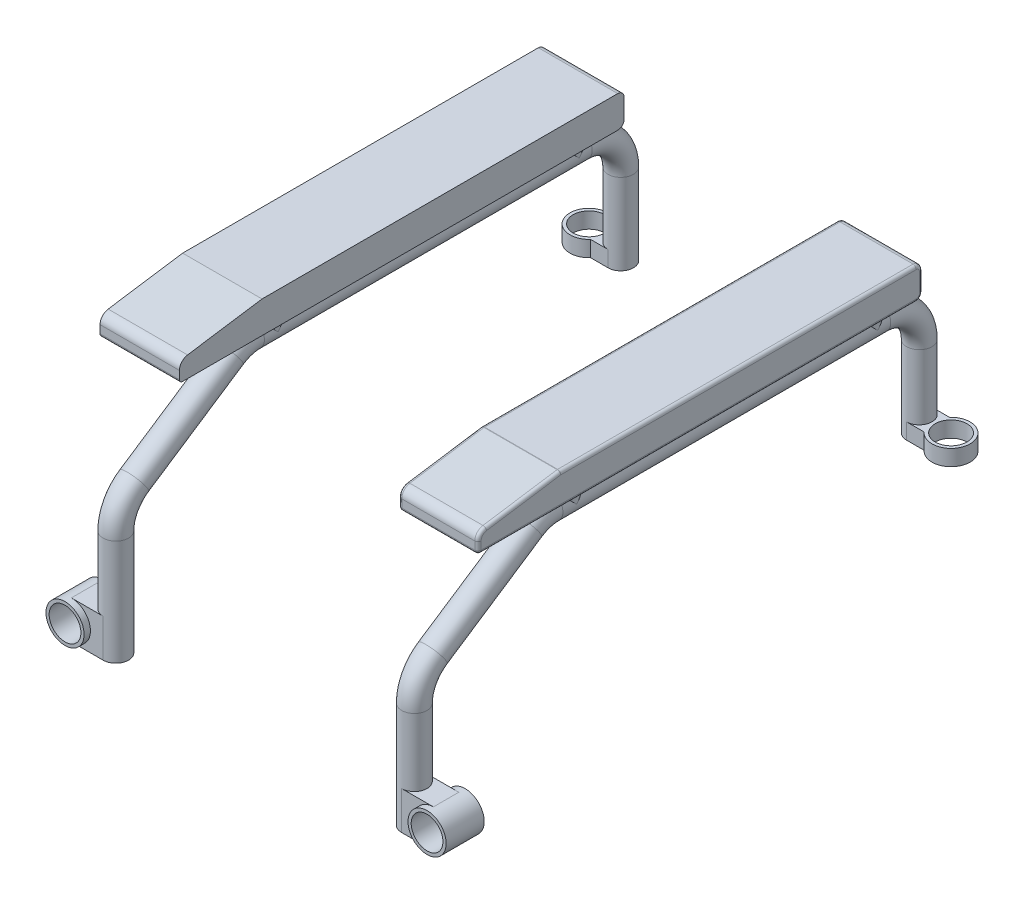
SolidWorks part; units mm, degrees
ref_plane "Front Plane" through (0, 0, 0) normal (0, 0, 1) x (1, 0, 0)
ref_plane "Top Plane" through (0, 0, 0) normal (0, 1, 0) x (1, 0, 0)
ref_plane "Right Plane" through (0, 0, 0) normal (1, 0, 0) x (0, 0, -1)
sketch "Sketch1" plane through (0, 0, 0) normal (1, 0, 0) x (0, 0, -1)
  line L0 (0, 0) -> (342.9, 0) construction
  line L1 (342.9, 0) -> (342.9, 54.61) construction
  line L2 (0, 0) -> (0, 69.3262)
  line L3 (108.6557, 152.4) -> (370.84, 152.4)
  line L4 (403.86, 119.38) -> (403.86, 54.61)
  line L5 (98.7191, 183.1531) -> (98.7191, 100.5217) construction
  line L6 (-22.3454, 87.0701) -> (49.3966, 87.0701) construction
  line L7 (14.7972, 96.8625) -> (90.4328, 146.9163)
  arc A0 (403.86, 119.38) -> (370.84, 152.4) centre (370.84, 119.38) ccw
  arc A1 (108.6557, 152.4) -> (90.4328, 146.9163) centre (108.6557, 119.38) ccw
  arc A2 (0, 69.3262) -> (14.7972, 96.8625) centre (33.02, 69.3262) cw
  point P16 (98.7191, 152.4)
  point P19 (0, 87.0701)
  dimension "D1" = 33.02
  dimension "D2" = 33.02
sketch "Sketch2" plane through (0, 0, 0) normal (0, 1, 0) x (1, 0, 0)
  circle A0 centre (0, 0) radius 10.16
sweep "Sweep1" add profiles "Sketch2" path "Sketch1"
sketch "Sketch3" plane through (0, 0, 0) normal (0, -1, 0) x (1, 0, 0)
  line L0 (0, 0) -> (-25.4, 0)
  line L1 (0, -403.86) -> (-25.4, -403.86)
sketch "Sketch4" plane through (0, 0, 0) normal (0, 0, 1) x (1, 0, 0)
  line L0 (0, 0) -> (-25.4, 0) construction
  circle A0 centre (-25.4, 0) radius 15.24
extrude "Boss-Extrude1" add sketch "Sketch4" along normal blind 15.24 and the other way blind 15.24 separate body
sketch "Sketch5" plane through (0, 0, 0) normal (0, -1, 0) x (1, 0, 0)
  circle A1 centre (0, 0) radius 10.16
  circle A2 centre (0, 0) radius 10.16
  dimension "D1" = 0
extrude "Boss-Extrude2" add sketch "Sketch5" along normal blind 15.24
sketch "Sketch6" plane through (0, 0, 0) normal (1, 0, 0) x (0, 0, -1)
  line L0 (-10.16, -15.24) -> (-10.16, 15.24)
  line L1 (15.24, 15.24) -> (-15.24, 15.24) construction
  line L2 (-10.16, 69.3262) -> (-10.16, -15.24) construction
  line L3 (-10.16, 15.24) -> (10.16, 15.24)
  line L4 (10.16, 15.24) -> (10.16, -15.24)
  line L5 (-10.16, -15.24) -> (10.16, -15.24) construction
  line L6 (10.16, -15.24) -> (-10.16, -15.24)
extrude "Boss-Extrude3" add sketch "Sketch6" against normal blind 25.4
sketch "Sketch7" plane through (0, 0, 15.24) normal (0, 0, 1) x (1, 0, 0)
  circle A0 centre (-25.4, 0) radius 12.7
extrude "Cut-Extrude1" cut sketch "Sketch7" against normal through all
ref_plane "Plane1" through (0, 54.61, 0) normal (0, 1, 0) x (1, 0, 0)
sketch "Sketch8" plane through (0, 54.61, 0) normal (0, 1, 0) x (1, 0, 0)
  circle A0 centre (-25.4, 403.86) radius 15.24
extrude "Boss-Extrude4" add sketch "Sketch8" along normal blind 12.7 separate body
sketch "Sketch10" plane through (0, 0, 0) normal (1, 0, 0) x (0, 0, -1)
  line L0 (393.7, 54.61) -> (414.02, 54.61)
  line L1 (414.02, 54.61) -> (414.02, 67.31)
  line L2 (414.02, 54.61) -> (414.02, 119.38) construction
  line L3 (414.02, 67.31) -> (393.7, 67.31)
  line L4 (393.7, 119.38) -> (393.7, 54.61) construction
  line L5 (393.7, 67.31) -> (393.7, 54.61)
extrude "Boss-Extrude5" add sketch "Sketch10" against normal blind 25.4
sketch "Sketch11" plane through (0, 67.31, 0) normal (0, 1, 0) x (1, 0, 0)
  circle A0 centre (-25.4, 403.86) radius 12.7
extrude "Cut-Extrude2" cut sketch "Sketch11" against normal blind 25.4
ref_plane "Plane2" through (0, 152.4, 0) normal (0, 1, 0) x (1, 0, 0)
sketch "Sketch12" plane through (0, 152.4, 0) normal (0, 1, 0) x (1, 0, 0)
  line L0 (0, 370.84) -> (0, 108.6557) construction
  line L1 (10.16, 370.84) -> (-10.16, 370.84) construction
  line L2 (10.16, 108.6557) -> (-10.16, 108.6557) construction
  circle A0 centre (0, 360.4101) radius 10.16
  circle A1 centre (0, 119.554) radius 10.16
extrude "Boss-Extrude6" add sketch "Sketch12" along normal blind 25.4
sketch "Sketch13" plane through (0, 0, 0) normal (1, 0, 0) x (0, 0, -1)
  line L0 (369.6857, 177.8) -> (21.68, 177.8)
  line L1 (374.7657, 182.88) -> (374.7657, 198.12)
  line L2 (369.6857, 203.2) -> (85.1707, 203.2)
  line L3 (19.14, 180.34) -> (19.14, 186.6826)
  line L4 (25.6234, 194.2174) -> (85.1707, 203.2)
  arc A0 (19.14, 186.6826) -> (25.6234, 194.2174) centre (26.76, 186.6826) cw
  arc A4 (19.14, 180.34) -> (21.68, 177.8) centre (21.68, 180.34) ccw
  arc A5 (374.7657, 182.88) -> (369.6857, 177.8) centre (369.6857, 182.88) cw
  arc A6 (374.7657, 198.12) -> (369.6857, 203.2) centre (369.6857, 198.12) ccw
  dimension "D1" = 7.62
  dimension "D5" = 2.54
  dimension "D6" = 5.08
extrude "Boss-Extrude7" add sketch "Sketch13" along normal blind 31.75 and the other way blind 31.75
ref_plane "Plane3" through (119.38, 0, 0) normal (1, 0, 0) x (0, 0, -1)
mirror "Mirror1" about plane through (119.38, 0, 0) normal (1, 0, 0) of bodies 110
fillet "Fillet1" radius 2.54 18 edges at (207.01, 198.7087, -55.397) (207.01, 191.6527, -20.984) (207.01, 183.5113, -19.14) (207.01, 178.5439, -19.8839) (207.01, 177.8, -195.6829) (207.01, 179.2879, -373.2778) (207.01, 190.5, -374.7657) (207.01, 201.7121, -373.2778) (270.51, 198.7087, -55.397) (270.51, 191.6527, -20.984) (270.51, 183.5113, -19.14) (270.51, 178.5439, -19.8839) (270.51, 177.8, -195.6829) (270.51, 179.2879, -373.2778) (270.51, 190.5, -374.7657) (270.51, 201.7121, -373.2778) (207.01, 203.2, -227.4282) (270.51, 203.2, -227.4282)
fillet "Fillet2" radius 2.54 3 edges at (269.7661, 202.4561, -85.2265) (207.7539, 202.4561, -85.2265) (238.76, 203.2, -85.1707)
